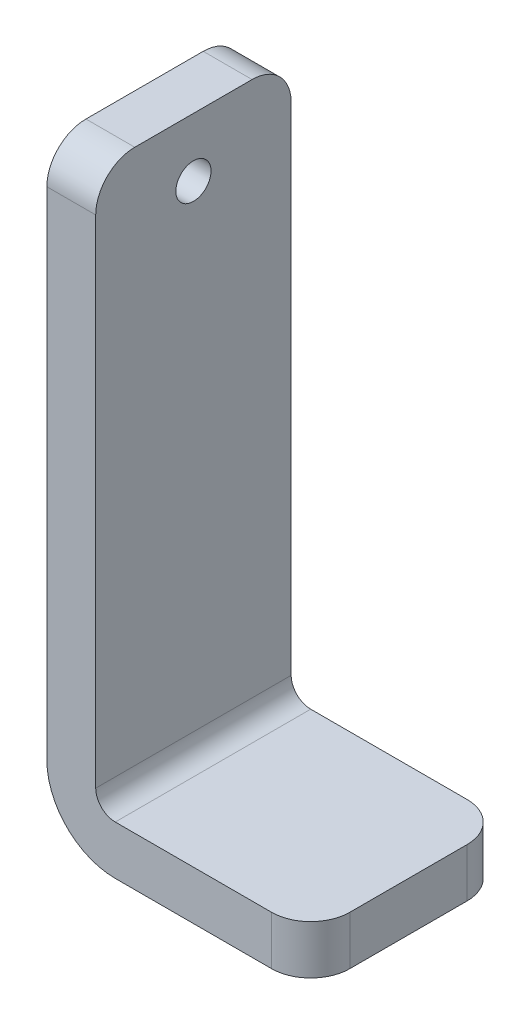
SolidWorks part; units mm, degrees
material "1060 Alloy"
ref_plane "Front Plane" through (0, 0, 0) normal (0, 0, 1) x (1, 0, 0)
ref_plane "Top Plane" through (0, 0, 0) normal (0, 1, 0) x (1, 0, 0)
ref_plane "Right Plane" through (0, 0, 0) normal (1, 0, 0) x (0, 0, -1)
sketch "Sketch1" plane through (0, 0, 0) normal (0, 0, 1) x (1, 0, 0)
  line L0 (0, 23.0683) -> (0, -11.7297)
  line L1 (1.27, -12.9997) -> (13.97, -12.9997)
  line L2 (-3.175, 23.0683) -> (-3.175, -11.7297)
  line L3 (1.27, -16.1747) -> (13.97, -16.1747)
  line L4 (0, 23.0683) -> (-3.175, 23.0683)
  line L5 (13.97, -12.9997) -> (13.97, -16.1747)
  arc A0 (1.27, -12.9997) -> (0, -11.7297) centre (1.27, -11.7297) cw
  arc A1 (1.27, -16.1747) -> (-3.175, -11.7297) centre (1.27, -11.7297) cw
  dimension "D1" = 1.27
  dimension "D3" = 12.7
  dimension "D4" = 34.798
  dimension "D2" = 3.175
extrude "Boss-Extrude1" add sketch "Sketch1" along normal blind 12.7
sketch "Sketch2" plane through (-3.175, 0, 0) normal (-1, 0, 0) x (0, 0, 1)
  line L0 (12.7, 23.0683) -> (0, 23.0683) construction
  line L1 (12.7, 23.0683) -> (0, 23.0683) construction
  line L6 (3.7, 17.0492) -> (4.353, 5.0991)
  line L7 (9, 17.0492) -> (8.347, 5.0991)
  circle A0 centre (6.35, 19.2583) radius 1.143
  arc A6 (9, 17.0492) -> (3.7, 17.0492) centre (6.35, 19.2583) ccw
  arc A7 (4.353, 5.0991) -> (8.347, 5.0991) centre (6.35, 5.2083) ccw
  circle A11 centre (6.35, 4.8083) radius 0.6
  circle A15 centre (6.35, 8.8083) radius 0.6
  circle A17 centre (6.35, 12.8083) radius 0.6
  point P13 (6.35, 23.0683)
  dimension "D1" = 6.9
  dimension "D2" = 4
  dimension "D7" = 1.2
  dimension "D8" = 6.45
  dimension "D10" = 2.286
  dimension "D3" = 11.95
  dimension "D4" = 0.653
  dimension "D5" = 5.3
  dimension "D6" = 3.994
  dimension "D9" = 4
  dimension "D11" = 4
  dimension "D12" = 3.81
extrude "Cut-Extrude1" cut sketch "Sketch2" against normal up to next from surface contours A0 starting at face at (-3.175, 5.6693, 6.35)
sketch "Sketch3" plane through (-3.175, 0, 0) normal (-1, 0, 0) x (0, 0, 1)
  line L0 (6.35, 23.0683) -> (6.35, -11.7297)
  line L1 (12.7, 23.0683) -> (0, 23.0683) construction
  line L2 (12.7, -11.7297) -> (0, -11.7297) construction
fillet "Fillet1" radius 2.54 4 edges at (13.97, -14.5872, 0) (13.97, -14.5872, 12.7) (-1.5875, 23.0683, 0) (-1.5875, 23.0683, 12.7)
